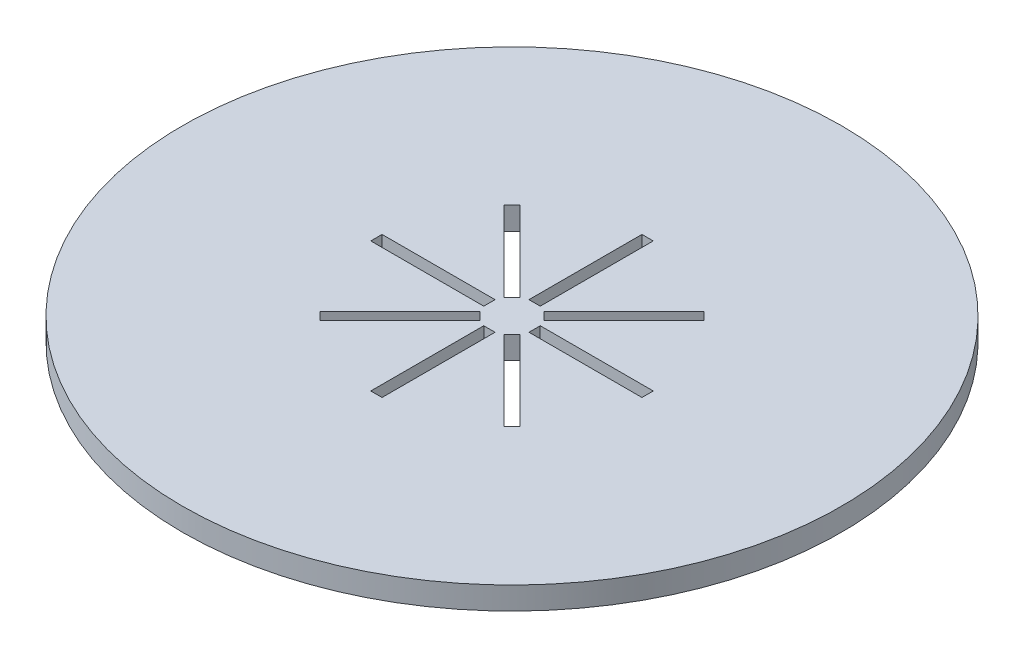
SolidWorks part; units mm, degrees
material "SS304"
ref_plane "Front Plane" through (0, 0, 0) normal (0, 0, 1) x (1, 0, 0)
ref_plane "Top Plane" through (0, 0, 0) normal (0, 1, 0) x (1, 0, 0)
ref_plane "Right Plane" through (0, 0, 0) normal (1, 0, 0) x (0, 0, -1)
sketch "Sketch1" plane through (0, 0, 0) normal (0, 1, 0) x (1, 0, 0)
  circle A0 centre (0, 0) radius 87.5
  dimension "D1" = 175
sheet metal parameters "Sheet-Metal1" thickness 6 parameters "D1"=5
base flange "Base-Flange1" sketch "Sketch1" thickness 6 reverse thickness direction no parameters "D1"=5
sketch "Sketch4" plane through (0, 0, 0) normal (0, 1, 0) x (1, 0, 0)
  line L1 (-36, 1.5) -> (-6, 1.5)
  line L2 (-36, 1.5) -> (-36, -1.5)
  line L3 (-36, -1.5) -> (-6, -1.5)
  line L4 (-6, 1.5) -> (-6, -1.5)
  circle A0 centre (0, 0) radius 6 construction
  point P7 (-6, 0)
  dimension "D1" = 12
  dimension "D2" = 3
  dimension "D3" = 30
extrude "Cut-Extrude1" cut sketch "Sketch4" against normal blind 10 normal cut yes
pattern_circular "CirPattern1" count 8 over 360 about axis through (0, 0, 0) along (0, 1, 0) of "Cut-Extrude1"
flat pattern "Flat-Pattern1" [suppressed]
sketch "Bend-Lines1" plane through (0, 0, 0) normal (0, 1, 0) x (1, 0, 0)
sketch "Bounding-Box1" [suppressed] plane through (0, 0, 0) normal (0, 1, 0) x (1, 0, 0)
